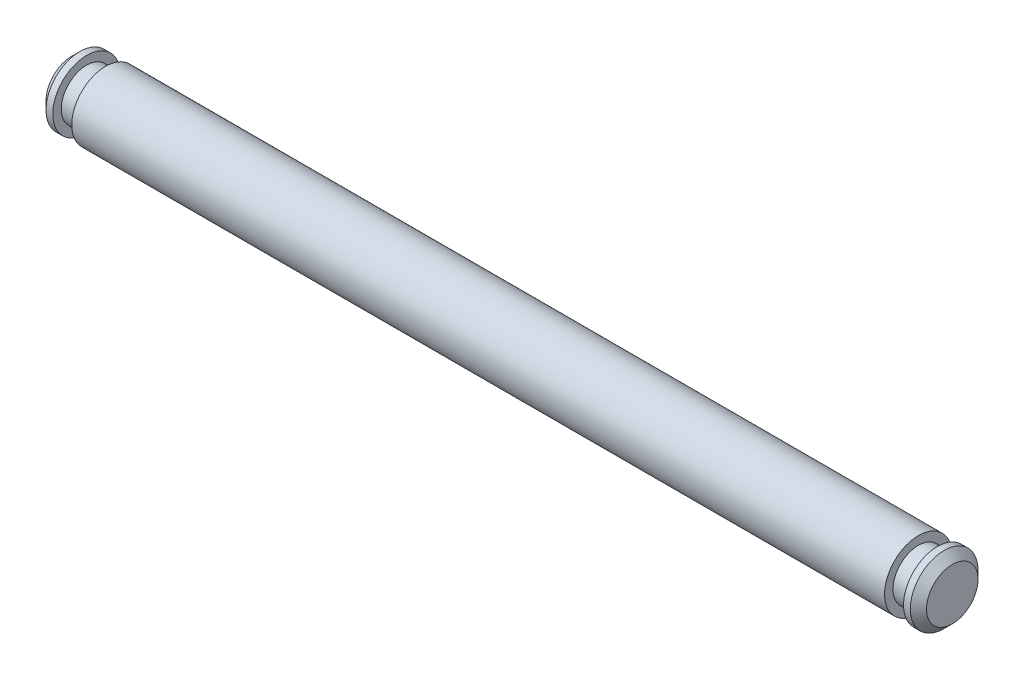
SolidWorks part; units mm, degrees
ref_plane "Front Plane" through (0, 0, 0) normal (0, 0, 1) x (1, 0, 0)
ref_plane "Top Plane" through (0, 0, 0) normal (0, 1, 0) x (1, 0, 0)
ref_plane "Right Plane" through (0, 0, 0) normal (1, 0, 0) x (0, 0, -1)
sketch "Sketch1" plane through (0, 0, 0) normal (0, 0, 1) x (1, 0, 0)
  line L0 (0, 0) -> (82.55, 0)
  line L1 (82.55, 0) -> (82.55, 2.413)
  line L2 (82.55, 2.413) -> (81.788, 3.175)
  line L3 (81.788, 3.175) -> (81.153, 3.175)
  line L4 (81.153, 3.175) -> (81.153, 2.3813)
  line L5 (81.153, 2.3813) -> (79.375, 2.3813)
  line L6 (79.375, 2.3813) -> (79.375, 3.175)
  line L7 (79.375, 3.175) -> (3.175, 3.175)
  line L8 (3.175, 3.175) -> (3.175, 2.3813)
  line L9 (3.175, 2.3813) -> (1.397, 2.3813)
  line L10 (1.397, 2.3813) -> (1.397, 3.175)
  line L11 (1.397, 3.175) -> (0.762, 3.175)
  line L12 (0.762, 3.175) -> (0, 2.413)
  line L13 (0, 2.413) -> (0, 0)
  line L14 (0, 0) -> (-4.8683, 0) construction
  dimension "D1" = 6.35
  dimension "D2" = 82.55
  dimension "D3" = 0.762
  dimension "D4" = 1.778
  dimension "D5" = 76.2
  dimension "D6" = 4.7625
revolve "Revolve1" add sketch "Sketch1" angle 360 about L14
